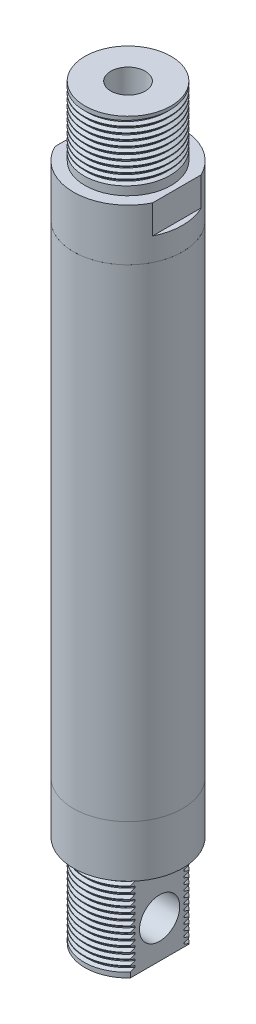
SolidWorks part; units mm, degrees
ref_plane "Front Plane" through (0, 0, 0) normal (0, 0, 1) x (1, 0, 0)
ref_plane "Top Plane" through (0, 0, 0) normal (0, 1, 0) x (1, 0, 0)
ref_plane "Right Plane" through (0, 0, 0) normal (1, 0, 0) x (0, 0, -1)
sketch "Sketch1" plane through (0, 0, 0) normal (0, 1, 0) x (1, 0, 0)
  circle A0 centre (0, 0) radius 7.5
  dimension "D1" = 15
extrude "Boss-Extrude1" add sketch "Sketch1" along normal blind 12
sketch "Sketch2" plane through (0, 0, 0) normal (0, -1, 0) x (1, 0, 0)
  circle A0 centre (0, 0) radius 9.5
  dimension "D1" = 19
extrude "Boss-Extrude2" add sketch "Sketch2" along normal blind 9 separate body
sketch "Sketch3" plane through (0, -9, 0) normal (0, -1, 0) x (1, 0, 0)
  circle A0 centre (0, 0) radius 9.5
  dimension "D1" = 19
extrude "Boss-Extrude3" add sketch "Sketch3" along normal blind 84 separate body
sketch "Sketch4" plane through (0, -93, 0) normal (0, -1, 0) x (1, 0, 0)
  circle A0 centre (0, 0) radius 9.5
  dimension "D1" = 19
extrude "Boss-Extrude4" add sketch "Sketch4" along normal blind 9 separate body
sketch "Sketch5" plane through (0, -102, 0) normal (0, -1, 0) x (1, 0, 0)
  circle A0 centre (0, 0) radius 7.5
  dimension "D1" = 15
extrude "Boss-Extrude5" add sketch "Sketch5" along normal blind 16 separate body
sketch "Sketch6" plane through (0, 12, 0) normal (0, 1, 0) x (1, 0, 0)
  circle A0 centre (0, 0) radius 3
  dimension "D1" = 6
extrude "Cut-Extrude1" cut sketch "Sketch6" against normal blind 164
thread "Thread1" pitch 1 method cut profile "Thread Profile1" start angle 0, offset 0, length 10, pitch 1, diameter 15
ref_plane "Plane1" through (-7.5, 12, 0) normal (0, 0, 1) x (-1, 0, 0)
sketch "Thread Profile1" plane through (-7.5, 12, 0) normal (0, 0, 1) x (-1, 0, 0)
  line L0 (0, 0) -> (0, 1) construction
  line L11 (0, 0) -> (0, 0.875)
  line L12 (0, 0.875) -> (-0.5413, 0.5625)
  line L13 (-0.5413, 0.5625) -> (-0.5413, 0.3125)
  line L15 (-0.5413, 0.3125) -> (0, 0)
  line L17 (-0.5413, 0.4375) -> (0, 0.4375) construction
  point P2 (0, 0)
  dimension "Pitch" = 1
  dimension "Profile_Angle" = 60
  dimension "Profile_Land" = 0.25
  dimension "Profile_Height" = 0.5413
thread "Thread2" pitch 1 method cut profile "Thread Profile2" start angle 0, offset 0, length 14, pitch 1, diameter 15
ref_plane "Plane2" through (7.5, -118, 0) normal (0, 0, 1) x (1, 0, 0)
sketch "Thread Profile2" plane through (7.5, -118, 0) normal (0, 0, 1) x (1, 0, 0)
  line L0 (0, 0) -> (0, 1) construction
  line L11 (0, 0) -> (0, 0.875)
  line L12 (0, 0.875) -> (-0.5413, 0.5625)
  line L13 (-0.5413, 0.5625) -> (-0.5413, 0.3125)
  line L15 (-0.5413, 0.3125) -> (0, 0)
  line L17 (-0.5413, 0.4375) -> (0, 0.4375) construction
  point P2 (0, 0)
  dimension "Pitch" = 1
  dimension "Profile_Angle" = 60
  dimension "Profile_Land" = 0.25
  dimension "Profile_Height" = 0.5413
sketch "Sketch21" plane through (0, -118, 0) normal (0, -1, 0) x (1, 0, 0)
  line L1 (-5.5, 5.099) -> (-5.5, -5.099)
  line L2 (5.5, 5.099) -> (5.5, -5.099)
  line L3 (-5.5, 5.099) -> (-10.1517, 5.099)
  line L4 (-5.5, 5.099) -> (-5.5, -5.099)
  line L5 (-5.5, -5.099) -> (-10.1517, -5.099)
  line L6 (-10.1517, 5.099) -> (-10.1517, -5.099)
  line L7 (5.5, 5.099) -> (10.2303, 5.099)
  line L8 (5.5, 5.099) -> (5.5, -5.099)
  line L9 (5.5, -5.099) -> (10.2303, -5.099)
  line L10 (10.2303, 5.099) -> (10.2303, -5.099)
  circle A1 centre (0, 0) radius 7.5 construction
  point P0 (0, 0)
  point P10 (-5.5, 0)
  point P13 (5.5, 0)
  circle M2 centre (0, 0) radius 7.5
extrude "Cut-Extrude3" cut sketch "Sketch21" against normal blind 15.5 contours L3 L6 L5 M2 | L10 L7 L9 M2 | L1 M2 | L2 M2 region at (-8.461, -118, 0) region at (-6.3099, -118, 0) region at (6.3099, -118, 0) region at (8.5015, -118, 0)
sketch "Sketch22" plane through (-5.5, 0, 0) normal (-1, 0, 0) x (0, 0, 1)
  line L0 (5.099, -118) -> (-5.099, -118) construction
  circle A0 centre (0, -111.5) radius 3.5
  dimension "D1" = 6.5
extrude "Cut-Extrude4" cut sketch "Sketch22" against normal blind 16
sketch "Sketch23" plane through (0, 0, 0) normal (0, 1, 0) x (1, 0, 0)
  line L2 (8.5, 6.259) -> (12.3718, 6.259)
  line L3 (8.5, 6.259) -> (8.5, -6.5814)
  line L4 (8.5, -6.5814) -> (12.3718, -6.5814)
  line L5 (12.3718, 6.259) -> (12.3718, -6.5814)
  line L6 (-8.5, 6.259) -> (-12.3032, 6.259)
  line L7 (-8.5, 6.259) -> (-8.5, -6.5814)
  line L8 (-8.5, -6.5814) -> (-12.3032, -6.5814)
  line L9 (-12.3032, 6.259) -> (-12.3032, -6.5814)
  point P4 (0, 0)
extrude "Cut-Extrude5" cut sketch "Sketch23" against normal blind 5
